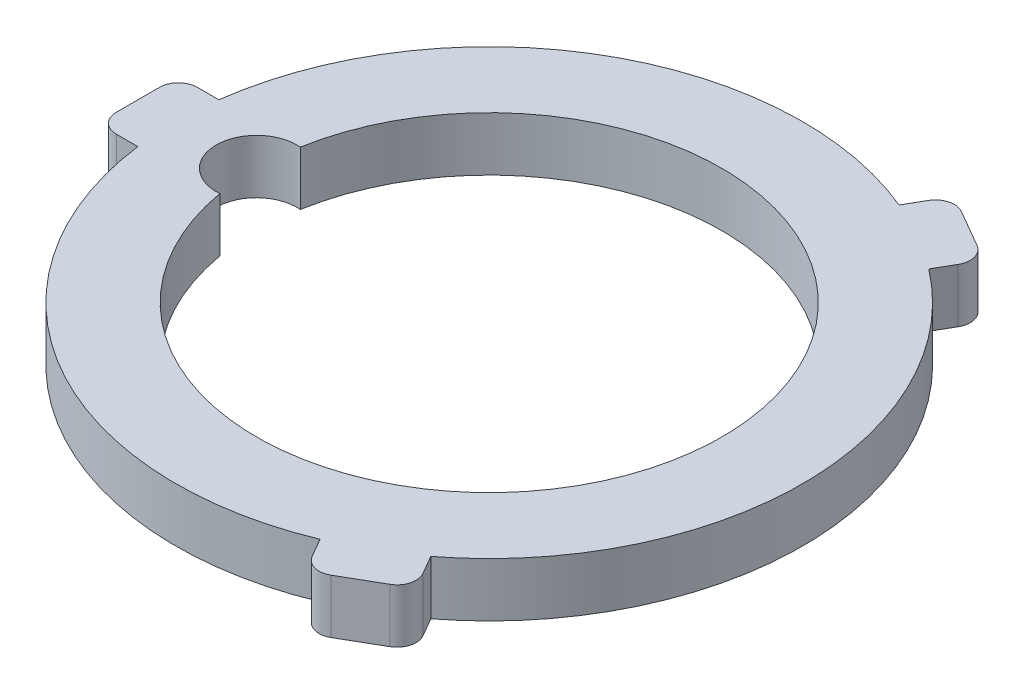
SolidWorks part; units mm, degrees
ref_plane "Ebene vorne" through (0, 0, 0) normal (0, 0, 1) x (1, 0, 0)
ref_plane "Ebene oben" through (0, 0, 0) normal (0, 1, 0) x (1, 0, 0)
ref_plane "Ebene rechts" through (0, 0, 0) normal (1, 0, 0) x (0, 0, -1)
sketch "Skizze1" plane through (0, 0, 0) normal (0, 1, 0) x (1, 0, 0)
  line L1 (-6.5, 0.75) -> (-5.2381, 0.75)
  line L2 (-6.5, 0.75) -> (-6.5, -0.75)
  line L3 (-6.5, -0.75) -> (-5.2381, -0.75)
  line L4 (-5.2381, 0.75) -> (-5.2381, -0.75)
  circle A0 centre (0, 0) radius 5.8
  circle A1 centre (0, 0) radius 4.3
extrude "Aufsatz-Linear austragen1" add sketch "Skizze1" along normal blind 1 contours A0
extrude "Aufsatz-Linear austragen2" add sketch "Skizze1<3>" along normal blind 1 contours L3 L4 L1 L2
sketch "Skizze1<3>" plane through (0, 0, 0) normal (0, 1, 0) x (1, 0, 0) same geometry as "Skizze1"
sketch "Skizze4" plane through (0, 1, 0) normal (0, 1, 0) x (1, 0, 0)
  circle A0 centre (0, 0) radius 4.305
extrude "Schnitt-Linear austragen1" cut sketch "Skizze4" against normal blind 1 contours A0
sketch "Skizze5" plane through (0, 1, 0) normal (0, 1, 0) x (1, 0, 0)
  circle A0 centre (0, 0) radius 4.305 construction
  circle A1 centre (-4.305, 0) radius 0.7477
extrude "Schnitt-Linear austragen2" cut sketch "Skizze5" against normal blind 1
pattern_circular "Kreismuster1" count 3 over 360 about axis through (0, 0, 0) along (0, 1, 0) of "Aufsatz-Linear austragen2"
fillet "Verrundung2" radius 0.35 6 edges at (2.6005, 0.5, 6.0042) (3.8995, 0.5, 5.2542) (3.8995, 0.5, -5.2542) (2.6005, 0.5, -6.0042) (-6.5, 0.5, 0.75) (-6.5, 0.5, -0.75)
